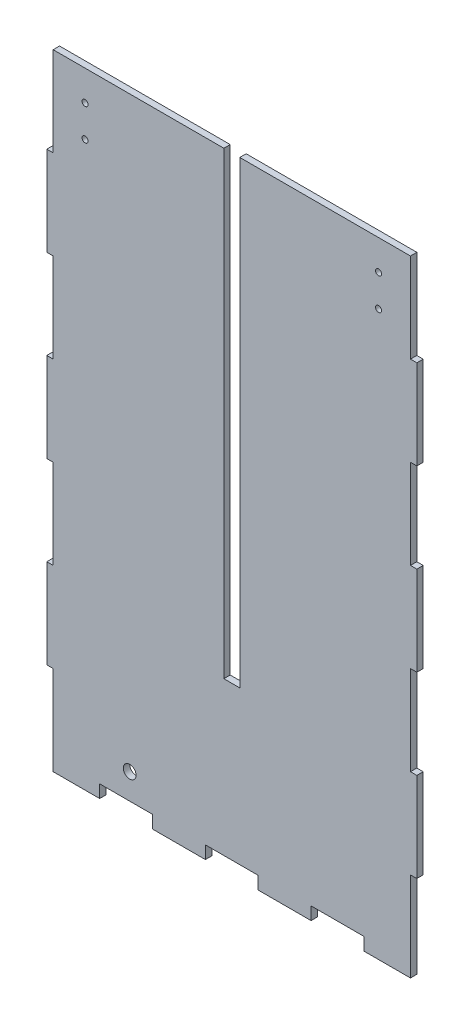
SolidWorks part; units mm, degrees
ref_plane "Front Plane" through (0, 0, 0) normal (0, 0, 1) x (1, 0, 0)
ref_plane "Top Plane" through (0, 0, 0) normal (0, 1, 0) x (1, 0, 0)
ref_plane "Right Plane" through (0, 0, 0) normal (1, 0, 0) x (0, 0, -1)
sketch "Sketch2" plane through (0, 0, 0) normal (0, 0, 1) x (1, 0, 0)
  line L0 (0, 152.4) -> (0, -152.4) construction
  line L1 (-88.9, 152.4) -> (88.9, 152.4)
  line L2 (-88.9, 152.4) -> (-88.9, -152.4)
  line L3 (-88.9, -152.4) -> (88.9, -152.4)
  line L4 (88.9, 152.4) -> (88.9, -152.4)
  line L5 (-88.9, 107.95) -> (-88.9, 63.5)
  line L6 (-88.9, 152.4) -> (-92.075, 152.4)
  line L7 (-88.9, 152.4) -> (-88.9, 107.95)
  line L8 (-88.9, 107.95) -> (-92.075, 107.95)
  line L9 (-92.075, 152.4) -> (-92.075, 107.95)
  line L10 (88.9, 152.4) -> (92.075, 152.4)
  line L11 (88.9, 152.4) -> (88.9, 107.95)
  line L12 (88.9, 107.95) -> (92.075, 107.95)
  line L13 (92.075, 152.4) -> (92.075, 107.95)
  line L14 (-65.7679, -152.4) -> (-92.075, -152.4)
  line L15 (-65.7679, -152.4) -> (-65.7679, -158.75)
  line L16 (-65.7679, -158.75) -> (-92.075, -158.75)
  line L17 (-92.075, -152.4) -> (-92.075, -158.75)
  line L18 (-88.9, 107.95) -> (-92.075, 107.95)
  line L19 (-92.075, 107.95) -> (-92.075, 63.5)
  line L20 (-88.9, 63.5) -> (-92.075, 63.5)
  line L21 (88.9, 107.95) -> (88.9, 63.5)
  line L22 (88.9, 107.95) -> (92.075, 107.95)
  line L23 (92.075, 107.95) -> (92.075, 63.5)
  line L24 (88.9, 63.5) -> (92.075, 63.5)
  line L25 (-88.9, 63.5) -> (-88.9, 19.05)
  line L26 (-88.9, 63.5) -> (-92.075, 63.5)
  line L27 (-92.075, 63.5) -> (-92.075, 19.05)
  line L28 (-88.9, 19.05) -> (-92.075, 19.05)
  line L29 (88.9, 63.5) -> (88.9, 19.05)
  line L30 (88.9, 63.5) -> (92.075, 63.5)
  line L31 (92.075, 63.5) -> (92.075, 19.05)
  line L32 (88.9, 19.05) -> (92.075, 19.05)
  line L33 (-88.9, 19.05) -> (-88.9, -25.4)
  line L34 (-88.9, 19.05) -> (-92.075, 19.05)
  line L35 (-92.075, 19.05) -> (-92.075, -25.4)
  line L36 (-88.9, -25.4) -> (-92.075, -25.4)
  line L37 (88.9, 19.05) -> (88.9, -25.4)
  line L38 (88.9, 19.05) -> (92.075, 19.05)
  line L39 (92.075, 19.05) -> (92.075, -25.4)
  line L40 (88.9, -25.4) -> (92.075, -25.4)
  line L41 (-88.9, -25.4) -> (-88.9, -69.85)
  line L42 (-88.9, -25.4) -> (-92.075, -25.4)
  line L43 (-92.075, -25.4) -> (-92.075, -69.85)
  line L44 (-88.9, -69.85) -> (-92.075, -69.85)
  line L45 (88.9, -25.4) -> (88.9, -69.85)
  line L46 (88.9, -25.4) -> (92.075, -25.4)
  line L47 (92.075, -25.4) -> (92.075, -69.85)
  line L48 (88.9, -69.85) -> (92.075, -69.85)
  line L49 (-88.9, -69.85) -> (-88.9, -114.3)
  line L50 (-88.9, -69.85) -> (-92.075, -69.85)
  line L51 (-92.075, -69.85) -> (-92.075, -114.3)
  line L52 (-88.9, -114.3) -> (-92.075, -114.3)
  line L53 (88.9, -69.85) -> (88.9, -114.3)
  line L54 (88.9, -69.85) -> (92.075, -69.85)
  line L55 (92.075, -69.85) -> (92.075, -114.3)
  line L56 (88.9, -114.3) -> (92.075, -114.3)
  line L57 (-88.9, -114.3) -> (-88.9, -158.75)
  line L58 (-88.9, -114.3) -> (-92.075, -114.3)
  line L59 (-92.075, -114.3) -> (-92.075, -158.75)
  line L60 (-88.9, -158.75) -> (-92.075, -158.75)
  line L61 (88.9, -114.3) -> (88.9, -158.75)
  line L62 (88.9, -114.3) -> (92.075, -114.3)
  line L63 (92.075, -114.3) -> (92.075, -158.75)
  line L64 (88.9, -158.75) -> (92.075, -158.75)
  line L65 (-39.4607, -152.4) -> (-39.4607, -158.75)
  line L66 (-39.4607, -152.4) -> (-65.7679, -152.4)
  line L67 (-65.7679, -152.4) -> (-65.7679, -158.75)
  line L68 (-39.4607, -158.75) -> (-65.7679, -158.75)
  line L69 (-13.1536, -152.4) -> (-13.1536, -158.75)
  line L70 (-13.1536, -152.4) -> (-39.4607, -152.4)
  line L71 (-39.4607, -152.4) -> (-39.4607, -158.75)
  line L72 (-13.1536, -158.75) -> (-39.4607, -158.75)
  line L73 (13.1536, -152.4) -> (13.1536, -158.75)
  line L74 (13.1536, -152.4) -> (-13.1536, -152.4)
  line L75 (-13.1536, -152.4) -> (-13.1536, -158.75)
  line L76 (13.1536, -158.75) -> (-13.1536, -158.75)
  line L77 (39.4607, -152.4) -> (39.4607, -158.75)
  line L78 (39.4607, -152.4) -> (13.1536, -152.4)
  line L79 (13.1536, -152.4) -> (13.1536, -158.75)
  line L80 (39.4607, -158.75) -> (13.1536, -158.75)
  line L81 (65.7679, -152.4) -> (65.7679, -158.75)
  line L82 (65.7679, -152.4) -> (39.4607, -152.4)
  line L83 (39.4607, -152.4) -> (39.4607, -158.75)
  line L84 (65.7679, -158.75) -> (39.4607, -158.75)
  line L85 (92.075, -152.4) -> (92.075, -158.75)
  line L86 (92.075, -152.4) -> (65.7679, -152.4)
  line L87 (65.7679, -152.4) -> (65.7679, -158.75)
  line L88 (92.075, -158.75) -> (65.7679, -158.75)
  point P6 (0, 0)
  dimension "D1" = 177.8
  dimension "D2" = 184.15
  dimension "D3" = 304.8
  dimension "D4" = 311.15
  dimension "D6" = 44.45
  dimension "D8" = 26.3071
  dimension "D5" = 7
  dimension "D7" = 7
extrude "Boss-Extrude1" add sketch "Sketch2" along normal blind 3.175 contours L0 L1 L2 L3 | L1 L0 L3 L4 | L20 L2 L8 L19 | L36 L2 L28 L35 | L52 L2 L44 L51 | L3 L57 L16 L15 | L72 L69 L3 L65 | L80 L77 L3 L73 | L4 L56 L55 L48 | L4 L40 L39 L32 | L4 L24 L23 L12 | L88 L61 L3 L81 region at (44.45, 0, 0) region at (-44.45, 0, 0) region at (-26.3071, -155.575, 0) region at (26.3071, -155.575, 0) region at (-90.4875, 85.725, 0) region at (90.4875, 85.725, 0) region at (-77.3339, -155.575, 0) region at (77.3339, -155.575, 0) region at (-90.4875, -3.175, 0) region at (90.4875, -3.175, 0) region at (-90.4875, -92.075, 0) region at (90.4875, -92.075, 0)
sketch "Sketch3" plane through (0, 0, 3.175) normal (0, 0, 1) x (1, 0, 0)
  line L0 (-88.9, 152.4) -> (88.9, 152.4) construction
  line L1 (-3.9688, 152.4) -> (3.9687, 152.4)
  line L2 (-3.9688, 152.4) -> (-3.9687, -76.2)
  line L3 (-3.9687, -76.2) -> (3.9688, -76.2)
  line L4 (3.9687, 152.4) -> (3.9688, -76.2)
  line L5 (0, -76.2) -> (0, 0) construction
  dimension "D1" = 7.9375
  dimension "D2" = 228.6
extrude "Cut-Extrude1" cut sketch "Sketch3" against normal through all
sketch "Sketch4" plane through (0, 0, 3.175) normal (0, 0, 1) x (1, 0, 0)
  line L0 (-65.7679, -152.4) -> (-39.4607, -152.4) construction
  line L1 (-88.9, -114.3) -> (-88.9, -158.75) construction
  circle A0 centre (-50.8, -139.7) radius 3.175
  dimension "D1" = 6.35
  dimension "D2" = 12.7
  dimension "D3" = 38.1
extrude "Cut-Extrude2" cut sketch "Sketch4" against normal through all
sketch "Sketch5" plane through (0, 0, 3.175) normal (0, 0, 1) x (1, 0, 0)
  line L0 (0, -152.4) -> (0, 152.4) construction
  line L1 (-13.1536, -152.4) -> (13.1536, -152.4) construction
  line L2 (3.9687, 152.4) -> (88.9, 152.4) construction
  line L3 (-88.9, 152.4) -> (-3.9688, 152.4) construction
  line L5 (-92.075, 107.95) -> (-92.075, 63.5) construction
  circle A0 centre (-73.025, 137.4) radius 1.5
  circle A1 centre (-73.025, 121.65) radius 1.5
  circle A2 centre (73.025, 121.65) radius 1.5
  circle A3 centre (73.025, 137.4) radius 1.5
  dimension "D1" = 15.75
  dimension "D2" = 15
  dimension "D4" = 3
  dimension "D5" = 3
  dimension "D3" = 19.05
extrude "Cut-Extrude3" cut sketch "Sketch5" against normal up to surface (3.175 mm away) up to face at (-47.625, -139.7, 0)
sketch "Sketch6" [suppressed] plane through (0, 0, 3.175) normal (0, 0, 1) x (1, 0, 0)
  line L1 (-92.075, 63.5) -> (-88.9, 63.5)
  line L2 (-92.075, 63.5) -> (-92.075, 19.05)
  line L3 (-92.075, 19.05) -> (-88.9, 19.05)
  line L4 (-88.9, 63.5) -> (-88.9, 19.05)
  line L5 (-92.075, -25.4) -> (-88.9, -25.4)
  line L6 (-92.075, -25.4) -> (-92.075, -69.85)
  line L7 (-92.075, -69.85) -> (-88.9, -69.85)
  line L8 (-88.9, -25.4) -> (-88.9, -69.85)
  line L9 (92.075, 63.5) -> (88.9, 63.5)
  line L10 (92.075, 63.5) -> (92.075, 19.05)
  line L11 (92.075, 19.05) -> (88.9, 19.05)
  line L12 (88.9, 63.5) -> (88.9, 19.05)
  line L13 (88.9, -25.4) -> (92.075, -25.4)
  line L14 (88.9, -25.4) -> (88.9, -69.85)
  line L15 (88.9, -69.85) -> (92.075, -69.85)
  line L16 (92.075, -25.4) -> (92.075, -69.85)
extrude "Boss-Extrude2" [suppressed] add sketch "Sketch6" against normal up to surface (3.175 mm away) up to face at (74.525, 137.4, 0)
sketch "Sketch7" [suppressed] plane through (0, 0, 3.175) normal (0, 0, 1) x (1, 0, 0)
  line L1 (-39.4607, -152.4) -> (-13.1536, -152.4)
  line L2 (-39.4607, -152.4) -> (-39.4607, -158.75)
  line L3 (-39.4607, -158.75) -> (-13.1536, -158.75)
  line L4 (-13.1536, -152.4) -> (-13.1536, -158.75)
  line L5 (13.1536, -152.4) -> (39.4607, -152.4)
  line L6 (13.1536, -152.4) -> (13.1536, -158.75)
  line L7 (13.1536, -158.75) -> (39.4607, -158.75)
  line L8 (39.4607, -152.4) -> (39.4607, -158.75)
extrude "Cut-Extrude4" [suppressed] cut sketch "Sketch7" against normal up to surface (3.175 mm away) up to face at (74.525, 137.4, 0)
equation "\"Height\"= 12in"
equation "\"Depth\"= 7in"
equation "\"WallThickness\"= 0.125in"
equation "\"FloorThickness\"= 0.25in"
equation "\"D1@Sketch2\"=\"Depth\""
equation "\"D2@Sketch2\"=\"D1@Sketch2\"+2*\"WallThickness\""
equation "\"D3@Sketch2\"=\"Height\""
equation "\"D4@Sketch2\"=\"D3@Sketch2\"+\"FloorThickness\""
equation "\"D6@Sketch2\"=\"D4@Sketch2\"/\"D5@Sketch2\""
equation "\"D8@Sketch2\"=\"D2@Sketch2\"/\"D7@Sketch2\""
equation "\"D1@Boss-Extrude1\"=\"WallThickness\""
equation "\"Width\" = 30in"
